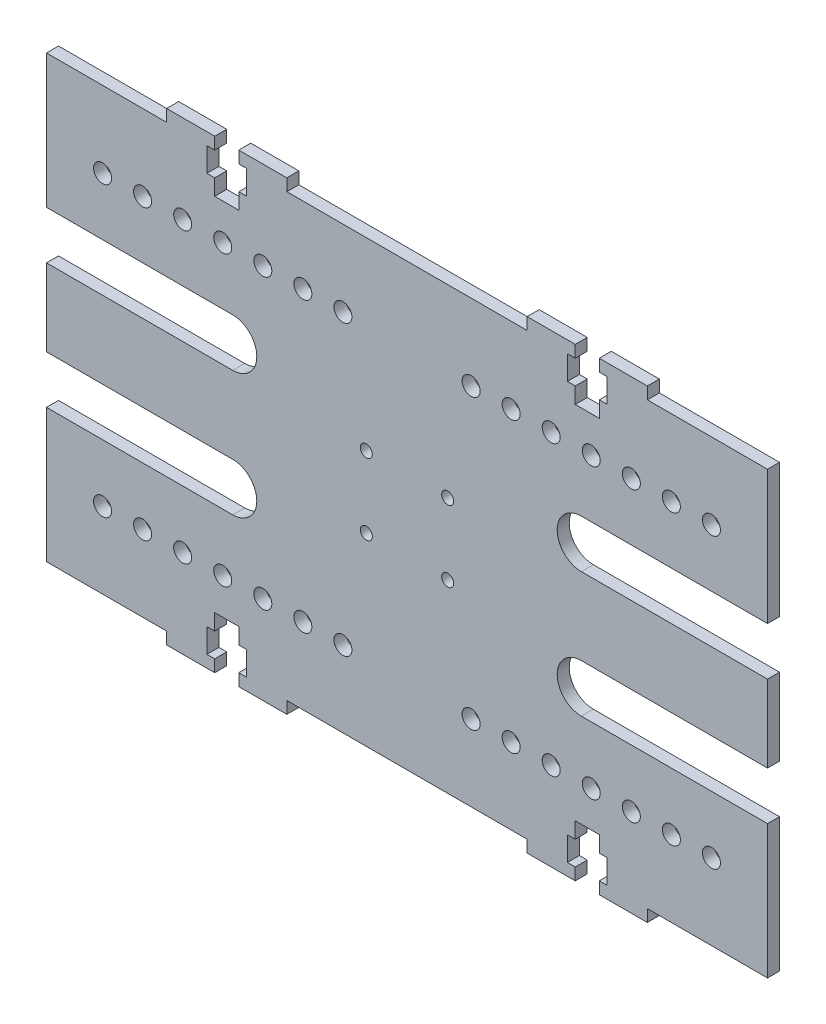
SolidWorks part; units mm, degrees
ref_plane "Front Plane" through (0, 0, 0) normal (0, 0, 1) x (1, 0, 0)
ref_plane "Top Plane" through (0, 0, 0) normal (0, 1, 0) x (1, 0, 0)
ref_plane "Right Plane" through (0, 0, 0) normal (1, 0, 0) x (0, 0, -1)
sketch "Sketch1" plane through (0, 0, 0) normal (0, 0, 1) x (1, 0, 0)
  line L0 (-90, -47) -> (-90, -21.621)
  line L1 (-90, -21.621) -> (-43.5, -21.621)
  line L2 (-43.5, -9.621) -> (-90, -9.621)
  line L3 (-90, -9.621) -> (-90, 9.621)
  line L4 (-90, 9.621) -> (-43.5, 9.621)
  line L5 (-43.5, 21.621) -> (-90, 21.621)
  line L6 (-90, 21.621) -> (-90, 47)
  line L7 (-87, 50) -> (87, 50)
  line L8 (90, 47) -> (90, 21.621)
  line L9 (90, 21.621) -> (43.5, 21.621)
  line L10 (43.5, 9.621) -> (90, 9.621)
  line L11 (90, 9.621) -> (90, -9.621)
  line L12 (90, -9.621) -> (43.5, -9.621)
  line L13 (43.5, -21.621) -> (90, -21.621)
  line L14 (90, -21.621) -> (90, -47)
  line L15 (87, -50) -> (-87, -50)
  arc A0 (-43.5, -21.621) -> (-43.5, -9.621) centre (-43.5, -15.621) ccw
  arc A1 (-43.5, 9.621) -> (-43.5, 21.621) centre (-43.5, 15.621) ccw
  arc A2 (-90, 47) -> (-87, 50) centre (-87, 47) cw
  arc A3 (87, 50) -> (90, 47) centre (87, 47) cw
  arc A4 (43.5, 21.621) -> (43.5, 9.621) centre (43.5, 15.621) ccw
  arc A5 (43.5, -9.621) -> (43.5, -21.621) centre (43.5, -15.621) ccw
  arc A6 (90, -47) -> (87, -50) centre (87, -47) cw
  arc A7 (-87, -50) -> (-90, -47) centre (-87, -47) cw
  circle A8 centre (-76, -36) radius 2.25
  circle A9 centre (-66, -36) radius 2.25
  circle A10 centre (-56, -36) radius 2.25
  circle A11 centre (-46, -36) radius 2.25
  circle A12 centre (-36, -36) radius 2.25
  circle A13 centre (-26, -36) radius 2.25
  circle A14 centre (-16, -36) radius 2.25
  circle A15 centre (16, -36) radius 2.25
  circle A16 centre (26, -36) radius 2.25
  circle A17 centre (36, -36) radius 2.25
  circle A18 centre (46, -36) radius 2.25
  circle A19 centre (56, -36) radius 2.25
  circle A20 centre (66, -36) radius 2.25
  circle A21 centre (76, -36) radius 2.25
  circle A22 centre (-76, 36) radius 2.25
  circle A23 centre (-66, 36) radius 2.25
  circle A24 centre (-56, 36) radius 2.25
  circle A25 centre (-46, 36) radius 2.25
  circle A26 centre (-36, 36) radius 2.25
  circle A27 centre (-26, 36) radius 2.25
  circle A28 centre (-16, 36) radius 2.25
  circle A29 centre (16, 36) radius 2.25
  circle A30 centre (26, 36) radius 2.25
  circle A31 centre (36, 36) radius 2.25
  circle A32 centre (46, 36) radius 2.25
  circle A33 centre (56, 36) radius 2.25
  circle A34 centre (66, 36) radius 2.25
  circle A35 centre (76, 36) radius 2.25
extrude "Plate_thickness" add sketch "Sketch1" along normal blind 3
sketch "草图2" plane through (0, 0, 3) normal (0, 0, 1) x (1, 0, 0)
  line L0 (87, 50) -> (-87, 50) construction
  line L1 (-90, 47) -> (90, 47)
  line L2 (-90, 47) -> (-90, 55)
  line L3 (-90, 55) -> (90, 55)
  line L4 (90, 47) -> (90, 55)
  line L5 (-90, -47) -> (90, -47)
  line L6 (-90, -47) -> (-90, -55)
  line L7 (-90, -55) -> (90, -55)
  line L8 (90, -47) -> (90, -55)
  line L9 (-87, -50) -> (87, -50) construction
  line L10 (0, 47) -> (0, -47)
  line L11 (0, 0) -> (61.7104, 0)
  line L12 (48, 45) -> (42, 45)
  line L13 (-60, 55) -> (-30, 55)
  line L14 (-60, 55) -> (-60, 58)
  line L15 (-60, 58) -> (-30, 58)
  line L16 (-30, 55) -> (-30, 58)
  line L17 (-48, 58) -> (-42, 58)
  line L18 (-48, 58) -> (-48, 45)
  line L19 (-48, 45) -> (-42, 45)
  line L20 (-42, 58) -> (-42, 45)
  line L21 (-49.95, 55) -> (-40.05, 55)
  line L22 (-49.95, 55) -> (-49.95, 49)
  line L23 (-49.95, 49) -> (-40.05, 49)
  line L24 (-40.05, 55) -> (-40.05, 49)
  line L25 (42, 58) -> (42, 45)
  line L26 (48, 58) -> (42, 58)
  line L27 (48, 58) -> (48, 45)
  line L28 (49.95, 49) -> (40.05, 49)
  line L29 (40.05, 55) -> (40.05, 49)
  line L30 (49.95, 55) -> (40.05, 55)
  line L31 (49.95, 55) -> (49.95, 49)
  line L32 (60, 58) -> (30, 58)
  line L33 (30, 55) -> (30, 58)
  line L34 (60, 55) -> (30, 55)
  line L35 (60, 55) -> (60, 58)
  line L36 (49.95, -55) -> (49.95, -49)
  line L37 (49.95, -55) -> (40.05, -55)
  line L38 (40.05, -55) -> (40.05, -49)
  line L39 (49.95, -49) -> (40.05, -49)
  line L40 (48, -58) -> (48, -45)
  line L41 (48, -58) -> (42, -58)
  line L42 (42, -58) -> (42, -45)
  line L43 (48, -45) -> (42, -45)
  line L44 (60, -55) -> (60, -58)
  line L45 (60, -55) -> (30, -55)
  line L46 (30, -55) -> (30, -58)
  line L47 (60, -58) -> (30, -58)
  line L48 (-49.95, -49) -> (-40.05, -49)
  line L49 (-40.05, -55) -> (-40.05, -49)
  line L50 (-49.95, -55) -> (-40.05, -55)
  line L51 (-49.95, -55) -> (-49.95, -49)
  line L52 (-48, -45) -> (-42, -45)
  line L53 (-42, -58) -> (-42, -45)
  line L54 (-48, -58) -> (-42, -58)
  line L55 (-48, -58) -> (-48, -45)
  line L56 (-60, -58) -> (-30, -58)
  line L57 (-30, -55) -> (-30, -58)
  line L58 (-60, -55) -> (-30, -55)
  line L59 (-60, -55) -> (-60, -58)
  line L61 (-10.16, 8.89) -> (10.16, 8.89)
  line L62 (-10.16, 8.89) -> (-10.16, -8.89)
  line L63 (-10.16, -8.89) -> (10.16, -8.89)
  line L64 (10.16, 8.89) -> (10.16, -8.89)
  line L65 (-10.16, 8.89) -> (10.16, -8.89) construction
  line L66 (-10.16, -8.89) -> (10.16, 8.89) construction
  circle A0 centre (-10.16, 8.89) radius 1.5
  circle A1 centre (10.16, 8.89) radius 1.5
  circle A2 centre (10.16, -8.89) radius 1.5
  circle A3 centre (-10.16, -8.89) radius 1.5
  dimension "D14" = 3
  dimension "D15" = 3
  dimension "D16" = 3
  dimension "D17" = 3
  dimension "D1" = 5
  dimension "D2" = 5
  dimension "D3" = 30
  dimension "D4" = 3
  dimension "D5" = 30
  dimension "D6" = 6
  dimension "D7" = 13
  dimension "D8" = 12
  dimension "D9" = 6
  dimension "D10" = 1.95
  dimension "D11" = 9.9
  dimension "D12" = 20.32
  dimension "D13" = 17.78
extrude "凸台-拉伸2" add sketch "草图2" against normal up to surface (3 mm away) contours L23 L22 L3 L2 L1 L18 | L29 L3 L13 L24 L23 L20 L1 L25 L28 | L15 L20 L3 L13 L16 | L18 L15 L14 L3 L13 | L3 L31 L28 L27 L1 L4 | L3 L35 L32 L27 | L33 L3 L25 L32 | L53 L48 L49 L7 L38 L39 L42 L5 | L40 L39 L36 L7 L8 L5 | L48 L55 L5 L6 L7 L51 | L7 L59 L56 L55 | L57 L7 L50 L53 L56 | L47 L42 L7 L46 | L47 L44 L7 L37 L40 region at (-69.7225, 50.9639, 3) region at (0, -50.9639, 3) region at (0, 50.9639, 3) region at (-54, 56.5, 3) region at (-36, 56.5, 3) region at (69.7225, 50.9639, 3) region at (36, 56.5, 3) region at (54, 56.5, 3) region at (-69.7225, -50.9639, 3) region at (69.7225, -50.9639, 3) region at (-36, -56.5, 3) region at (36, -56.5, 3) region at (-54, -56.5, 3) region at (54, -56.5, 3) up to face at (68.25, 36, 0)
extrude "切除-拉伸1" cut sketch "草图2<3>" against normal up to surface (3 mm away) contours L18 L23 L20 L13 | L23 L18 L1 L20 | L20 L1 L18 L19 | L24 L3 L20 L23 | L22 L23 L18 L13 | L3 L29 L28 L25 | L28 L27 L3 L25 | L31 L3 L27 L28 | L27 L28 L25 L1 | L27 L1 L25 L12 | L40 L43 L42 L5 | L42 L39 L40 L5 | L42 L37 L40 L39 | L7 L42 L39 L38 | L40 L37 L36 L39 | L55 L5 L53 L52 | L55 L48 L53 L5 | L55 L50 L53 L48 | L7 L55 L48 L51 | L53 L50 L49 L48 | L61 A0 L62 | L62 A0 L61 | L61 A1 L64 | L64 A1 L61 | L64 A2 L63 | L63 A2 L64 | L63 A3 L62 | L62 A3 L63 region at (-45, 48, 3) region at (-45, 46, 3) region at (-48.975, 52, 3) region at (-45, 52, 3) region at (-41.025, 52, 3) region at (45, 48, 3) region at (45, 46, 3) region at (41.025, 52, 3) region at (45, 52, 3) region at (-9.5234, 8.2534, 3) region at (-10.3722, 9.1022, 3) region at (10.3722, 9.1022, 3) region at (9.5234, 8.2534, 3) region at (48.975, 52, 3) region at (-10.3722, -9.1022, 3) region at (-9.5234, -8.2534, 3) region at (9.5234, -8.2534, 3) region at (10.3722, -9.1022, 3) region at (-45, -48, 3) region at (-45, -46, 3) region at (45, -46, 3) region at (45, -48, 3) region at (-45, -52, 3) region at (-41.025, -52, 3) region at (41.025, -52, 3) region at (45, -52, 3) region at (-48.975, -52, 3) region at (48.975, -52, 3) up to face at (0, 0, 0)
sketch "草图2<3>" plane through (0, 0, 3) normal (0, 0, 1) x (1, 0, 0) same geometry as "草图2"
